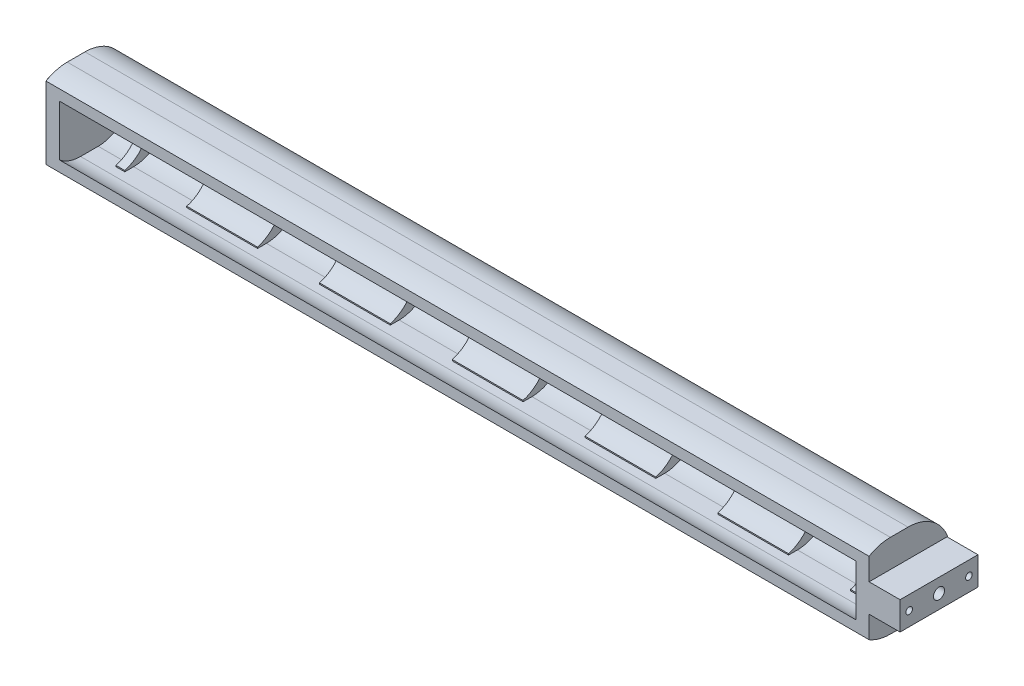
SolidWorks part; units mm, degrees
ref_plane "Ebene vorne" through (0, 0, 0) normal (0, 0, 1) x (1, 0, 0)
ref_plane "Ebene oben" through (0, 0, 0) normal (0, 1, 0) x (1, 0, 0)
ref_plane "Ebene rechts" through (0, 0, 0) normal (1, 0, 0) x (0, 0, -1)
sketch "Skizze2" plane through (0, 0, 0) normal (1, 0, 0) x (0, 0, -1)
  line L0 (-2, 0) -> (2, 0) construction
  line L1 (-2, 7.5) -> (2, 7.5)
  line L2 (-2, -7.5) -> (2, -7.5)
  line L3 (-2, 0) -> (2, 0) construction
  line L4 (-2, 9.5) -> (2, 9.5)
  line L5 (-2, -9.5) -> (2, -9.5)
  line L6 (-6.8043, 12.2143) -> (-6.8043, -12.1709)
  line L7 (0, 55) -> (0, -55) construction
  arc A0 (-2, 7.5) -> (-2, -7.5) centre (-2, 0) ccw
  arc A1 (2, -7.5) -> (2, 7.5) centre (2, 0) ccw
  arc A2 (-2, 9.5) -> (-2, -9.5) centre (-2, 0) ccw
  arc A3 (2, -9.5) -> (2, 9.5) centre (2, 0) ccw
  circle A4 centre (-2, 0) radius 7 construction
  point P2 (0, 0)
  point P10 (0, 0)
  dimension "D4" = 14
  dimension "D1" = 15
  dimension "D2" = 19
  dimension "D3" = 4
extrude "Aufsatz-Linear austragen1" add sketch "Skizze2" along normal blind 180 contours L5 A3 L4 A2 L6 A0 L1 A1 L2 region at (0, 7.2994, 4.6449)
sketch "Skizze3" plane through (0, 0, 0) normal (0, 0, 1) x (1, 0, 0)
  line L0 (38, 7.5) -> (38, -7.5)
  line L1 (6, 7.5) -> (8, 7.5)
  line L2 (6, 7.5) -> (6, -7.5)
  line L3 (6, -7.5) -> (8, -7.5)
  line L4 (8, 7.5) -> (8, -7.5)
  line L5 (6, 7.5) -> (8, -7.5) construction
  line L6 (6, -7.5) -> (8, 7.5) construction
  line L7 (36, 7.5) -> (36, -7.5)
  line L8 (0, -10.0674) -> (0, 10.0674) construction
  line L9 (36, 7.5) -> (38, 7.5)
  line L10 (36, -7.5) -> (38, -7.5)
  line L11 (180, 7.5) -> (0, 7.5) construction
  line L12 (180, -7.5) -> (0, -7.5) construction
  line L13 (10.0674, 0) -> (-10.0674, 0) construction
  line L14 (22, -7.5) -> (24, -7.5)
  line L15 (22, -7.5) -> (22, 7.5)
  line L16 (22, 7.5) -> (24, 7.5)
  line L17 (24, -7.5) -> (24, 7.5)
  line L18 (22, -7.5) -> (24, 7.5) construction
  line L19 (22, 7.5) -> (24, -7.5) construction
  line L20 (52, 7.5) -> (54, 7.5)
  line L21 (52, -7.5) -> (52, 7.5)
  line L22 (54, -7.5) -> (54, 7.5)
  line L23 (52, -7.5) -> (54, -7.5)
  line L24 (68, 7.5) -> (68, -7.5)
  line L25 (66, 7.5) -> (66, -7.5)
  line L26 (66, 7.5) -> (68, 7.5)
  line L27 (66, -7.5) -> (68, -7.5)
  line L28 (82, 7.5) -> (84, 7.5)
  line L29 (82, -7.5) -> (82, 7.5)
  line L30 (84, -7.5) -> (84, 7.5)
  line L31 (82, -7.5) -> (84, -7.5)
  line L32 (98, 7.5) -> (98, -7.5)
  line L33 (96, 7.5) -> (96, -7.5)
  line L34 (96, 7.5) -> (98, 7.5)
  line L35 (96, -7.5) -> (98, -7.5)
  line L36 (112, 7.5) -> (114, 7.5)
  line L37 (112, -7.5) -> (112, 7.5)
  line L38 (114, -7.5) -> (114, 7.5)
  line L39 (112, -7.5) -> (114, -7.5)
  line L40 (128, 7.5) -> (128, -7.5)
  line L41 (126, 7.5) -> (126, -7.5)
  line L42 (126, 7.5) -> (128, 7.5)
  line L43 (126, -7.5) -> (128, -7.5)
  line L44 (142, 7.5) -> (144, 7.5)
  line L45 (142, -7.5) -> (142, 7.5)
  line L46 (144, -7.5) -> (144, 7.5)
  line L47 (142, -7.5) -> (144, -7.5)
  line L48 (158, 7.5) -> (158, -7.5)
  line L49 (156, 7.5) -> (156, -7.5)
  line L50 (156, 7.5) -> (158, 7.5)
  line L51 (156, -7.5) -> (158, -7.5)
  line L52 (172, 7.5) -> (174, 7.5)
  line L53 (172, -7.5) -> (172, 7.5)
  line L54 (174, -7.5) -> (174, 7.5)
  line L55 (172, -7.5) -> (174, -7.5)
  circle A0 centre (15, 0) radius 7 construction
  circle A1 centre (45, 0) radius 7 construction
  circle A2 centre (75, 0) radius 7 construction
  circle A3 centre (105, 0) radius 7 construction
  circle A4 centre (135, 0) radius 7 construction
  circle A5 centre (165, 0) radius 7 construction
  point P4 (7, 0)
  point P11 (23, 0)
  dimension "D7" = 14
  dimension "D8" = 14
  dimension "D9" = 30
  dimension "D1" = 0
  dimension "D2" = 7
  dimension "D3" = 0
  dimension "D4" = 2
  dimension "D5" = 2
  dimension "D6" = 16
  dimension "D10" = 30
  dimension "D11" = 30
  dimension "D12" = 30
  dimension "D13" = 30
  dimension "D14" = 15
  dimension "D15" = 6
extrude "Aufsatz-Linear austragen2" add sketch "Skizze3" along normal blind 10 from offset 10 offset against normal yes
sketch "Skizze11" plane through (0, 0, 0) normal (0, 0, 1) x (1, 0, 0)
  line L0 (10.0674, 0) -> (-10.0674, 0) construction
  line L1 (24, -7.5) -> (36, -7.5)
  line L2 (24, -7.5) -> (24, 7.5)
  line L3 (24, 7.5) -> (36, 7.5)
  line L4 (36, -7.5) -> (36, 7.5)
  line L5 (24, -7.5) -> (36, 7.5) construction
  line L6 (24, 7.5) -> (36, -7.5) construction
  line L9 (24, -7.5) -> (24, 7.5) construction
  line L10 (54, 7.5) -> (66, 7.5)
  line L11 (66, -7.5) -> (66, 7.5)
  line L12 (54, -7.5) -> (66, -7.5)
  line L13 (54, -7.5) -> (54, 7.5)
  line L14 (84, 7.5) -> (96, 7.5)
  line L15 (96, -7.5) -> (96, 7.5)
  line L16 (84, -7.5) -> (96, -7.5)
  line L17 (84, -7.5) -> (84, 7.5)
  line L18 (114, 7.5) -> (126, 7.5)
  line L19 (126, -7.5) -> (126, 7.5)
  line L20 (114, -7.5) -> (126, -7.5)
  line L21 (114, -7.5) -> (114, 7.5)
  line L22 (144, 7.5) -> (156, 7.5)
  line L23 (156, -7.5) -> (156, 7.5)
  line L24 (144, -7.5) -> (156, -7.5)
  line L25 (144, -7.5) -> (144, 7.5)
  point P0 (30, 0)
  dimension "D1" = 0
  dimension "D2" = 15
  dimension "D3" = 5
extrude "Aufsatz-Linear austragen6" add sketch "Skizze11" along normal blind 10 from offset 10 offset against normal yes
sketch "Skizze5" plane through (0, 0, 0) normal (1, 0, 0) x (0, 0, -1)
  line L0 (12.6527, 0) -> (-12.6527, 0) construction
  line L1 (0, 7.2284) -> (0, -7.2284)
  line L2 (0, 10.45) -> (0, -10.45) construction
  line L3 (2, 0) -> (-2, 0) construction
  line L4 (2, -9.4759) -> (-2, -9.4759)
  line L5 (2, 9.4759) -> (-2, 9.4759)
  circle A0 centre (-2, 0) radius 7.5
  circle A3 centre (2, 0) radius 12.5141
  arc A4 (2, -9.4759) -> (2, 9.4759) centre (2, 0) ccw
  arc A5 (-2, 9.4759) -> (-2, -9.4759) centre (-2, 0) ccw
  point P12 (0, 0)
  dimension "D1" = 15
  dimension "D2" = 2
  dimension "D3" = 2
extrude "Schnitt-Linear austragen3" cut sketch "Skizze5" along normal blind 200 contours L1 A0 | A5 L5 A4 L4 A3 region at (0, 0, -2.2882) region at (0, 0, -11.8149)
sketch "Skizze6" plane through (180, 0, 0) normal (1, 0, 0) x (0, 0, -1)
  line L0 (-2.0024, 0) -> (2.0024, 0) construction
  line L1 (10.0674, 0) -> (-10.0674, 0) construction
  line L2 (-2.0024, 9.5) -> (2.0024, 9.5)
  line L3 (-2.0024, -9.5) -> (2.0024, -9.5)
  line L4 (-6.8043, 8.1676) -> (-6.8043, -8.1676)
  arc A5 (-2.0024, 9.5) -> (-2.0024, -9.5) centre (-2.0024, 0) ccw
  arc A6 (2.0024, -9.5) -> (2.0024, 9.5) centre (2.0024, 0) ccw
  point P4 (0, 0)
  arc M1 (-2, -7.5) -> (-6.8043, -5.7592) centre (-2, 0) cw
  arc M3 (-6.8043, 5.7592) -> (-2, 7.5) centre (-2, 0) cw
  line M4 (-2, 7.5) -> (2, 7.5)
  arc M5 (2, 7.5) -> (2, -7.5) centre (2, 0) cw
  line M6 (2, -7.5) -> (-2, -7.5)
  line M14 (-6.8043, -5.7592) -> (-6.8043, -8.1676)
  arc M15 (-6.8043, -8.1676) -> (-2, -9.4759) centre (-2, 0) ccw
  arc M19 (-2, 9.4759) -> (-6.8043, 8.1676) centre (-2, 0) ccw
  line M20 (-6.8043, 8.1676) -> (-6.8043, 5.7592)
  line M23 (-2, -9.4759) -> (2, -9.4759)
  arc M24 (2, -9.4759) -> (2, 9.4759) centre (2, 0) ccw
  line M25 (2, 9.4759) -> (-2, 9.4759)
  dimension "D1" = 9.5
extrude "Aufsatz-Linear austragen3" add sketch "Skizze6" along normal blind 3 contours M25 M19 M20 M3 M4 M5 M6 M1 M14 M15 M23 M24 | L4 region at (180, 8.8889, 4.4204) region at (180, 0, -0.7926)
sketch "Skizze9" plane through (183, 0, 0) normal (1, 0, 0) x (0, 0, -1)
  line L0 (10.0674, 0) -> (-10.0674, 0) construction
  line L1 (-6.8043, -3.1691) -> (10.8043, -3.1691)
  line L2 (-6.8043, -3.1691) -> (-6.8043, 3.1691)
  line L3 (-6.8043, 3.1691) -> (10.8043, 3.1691)
  line L4 (10.8043, -3.1691) -> (10.8043, 3.1691)
  line L5 (-6.8043, -3.1691) -> (10.8043, 3.1691) construction
  line L6 (-6.8043, 3.1691) -> (10.8043, -3.1691) construction
  point P0 (2, 0)
  dimension "D1" = 2
extrude "Aufsatz-Linear austragen5" add sketch "Skizze9" along normal blind 7
sketch "Skizze10" plane through (190, 0, 0) normal (1, 0, 0) x (0, 0, -1)
  line L0 (10.0541, 0) -> (-10.0541, 0) construction
  circle A0 centre (-4.75, 0) radius 0.75
  circle A1 centre (8.75, 0) radius 0.75
  circle A2 centre (2, 0) radius 1.25
  dimension "D1" = 1.5
  dimension "D5" = 2.5
  dimension "D2" = 13.5
  dimension "D4" = 6.75
  dimension "D6" = 2
extrude "Schnitt-Linear austragen5" cut sketch "Skizze10" against normal blind 7
sketch "Skizze12" plane through (0, 0, 0) normal (-1, 0, 0) x (0, 0, 1)
  line L0 (-2.0002, 0) -> (2.0002, 0) construction
  line L1 (10.0541, 0) -> (-10.0541, 0) construction
  line L2 (-2.0002, 9.5) -> (2.0002, 9.5)
  line L3 (-2.0002, -9.5) -> (2.0002, -9.5)
  line L4 (6.8043, 8.1676) -> (6.8043, -8.1676)
  arc A0 (-2.0002, 9.5) -> (-2.0002, -9.5) centre (-2.0002, 0) ccw
  arc A1 (2.0002, -9.5) -> (2.0002, 9.5) centre (2.0002, 0) ccw
  point P5 (0, 0)
  line M1 (6.8043, 5.7592) -> (6.8043, 8.1676)
  arc M2 (6.8043, 8.1676) -> (2, 9.4759) centre (2, 0) ccw
  line M3 (2, 9.4759) -> (-2, 9.4759)
  arc M4 (-2, 9.4759) -> (-2, -9.4759) centre (-2, 0) ccw
  line M5 (-2, -9.4759) -> (2, -9.4759)
  arc M6 (2, -9.4759) -> (6.8043, -8.1676) centre (2, 0) ccw
  line M7 (6.8043, -8.1676) -> (6.8043, -5.7592)
  arc M8 (6.8043, -5.7592) -> (2, -7.5) centre (2, 0) cw
  line M9 (2, -7.5) -> (-2, -7.5)
  arc M10 (-2, -7.5) -> (-2, 7.5) centre (-2, 0) cw
  line M11 (-2, 7.5) -> (2, 7.5)
  arc M12 (2, 7.5) -> (6.8043, 5.7592) centre (2, 0) cw
  dimension "D1" = 9.5
extrude "Aufsatz-Linear austragen7" add sketch "Skizze12" along normal blind 3 contours M12 M1 M2 M3 M4 M5 M6 M7 M8 M9 M10 M11 | L4 region at (0, 6.9634, 6.541) region at (0, 0, -0.7926)
sketch "Skizze13" plane through (-3, 0, 0) normal (-1, 0, 0) x (0, 0, 1)
  line L5 (-5.5, 3.5) -> (1.5, 3.5)
  line L6 (-5.5, 3.5) -> (-5.5, -3.5)
  line L7 (-5.5, -3.5) -> (1.5, -3.5)
  line L8 (1.5, 3.5) -> (1.5, -3.5)
  line L9 (-5.5, 3.5) -> (1.5, -3.5) construction
  line L10 (-5.5, -3.5) -> (1.5, 3.5) construction
  dimension "D1" = 7
  dimension "D2" = 7
extrude "Aufsatz-Linear austragen8" add sketch "Skizze13" along normal blind 5
sketch "Skizze15" plane through (-8, 0, 0) normal (-1, 0, 0) x (0, 0, 1)
  line L0 (10.0541, 0) -> (-10.0541, 0) construction
  line L1 (-5.5, 3.5) -> (-5.5, -3.5) construction
  circle A0 centre (-2, 0) radius 1.75
  dimension "D2" = 3.5
  dimension "D1" = 3.5
extrude "Schnitt-Linear austragen6" cut sketch "Skizze15" against normal blind 5
